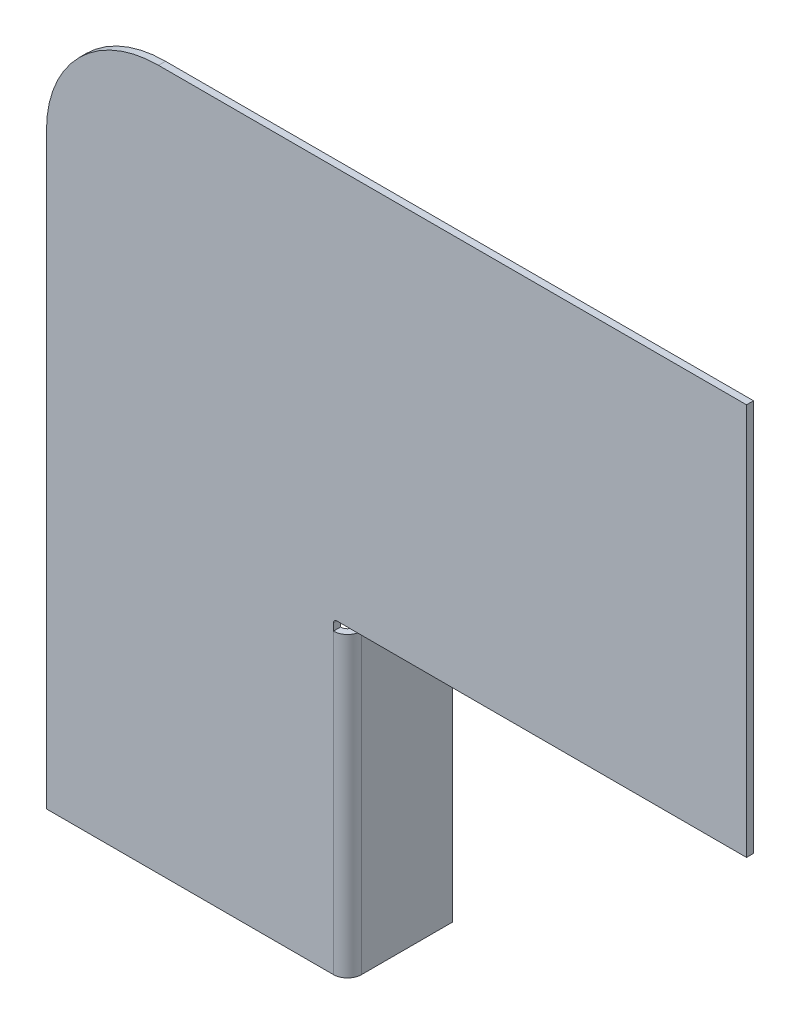
SolidWorks part; units mm, degrees
note: The reader was unsure of these and kept them because the rebuilt part matched: flange length of "Edge-Flange2".
ref_plane "Front Plane" through (0, 0, 0) normal (0, 0, 1) x (1, 0, 0)
ref_plane "Top Plane" through (0, 0, 0) normal (0, 1, 0) x (1, 0, 0)
ref_plane "Right Plane" through (0, 0, 0) normal (1, 0, 0) x (0, 0, -1)
sketch "Sketch1" plane through (0, 0, 0) normal (0, 0, 1) x (1, 0, 0)
  line L0 (-16, 0) -> (-16, -84)
  line L1 (-16, -84) -> (25, -84)
  line L2 (25, -84) -> (25, -40.5)
  line L3 (0, 16) -> (84, 16)
  line L4 (84, 16) -> (84, -40)
  line L5 (84, -40) -> (25.5, -40)
  arc A1 (0, 16) -> (-16, 0) centre (0, 0) ccw
  arc A2 (25.5, -40) -> (25, -40.5) centre (25.5, -40.5) ccw
  point P8 (42, -55)
  point P10 (42, -55)
  dimension "D1" = 56
  dimension "D4" = 1
  dimension "D5" = 41
  dimension "D6" = 16
  dimension "D2" = 84
  dimension "D3" = 84
base flange "Base-Flange1" sketch "Sketch1" thickness 1 reverse thickness direction no parameters "D1"=1
edge flange "Edge-Flange1" [suppressed] sketch "Sketch8" flange profiles "Sketch8", "Sketch10" flange angle 90 flange position material inside bend radius 1 thickness 1
sketch "Sketch8" plane through (0, -4, -1) normal (0, -1, 0) x (-1, 0, 0)
  line L0 (-19, 0) -> (-84, 0) construction
  line L1 (-19, 0) -> (-84, 0)
  line L2 (-84, 0) -> (-84, 19)
  line L3 (-84, 19) -> (-19, 19)
  line L4 (-19, 19) -> (-19, 0)
sketch "Sketch10" plane through (4, 0, -1) normal (1, 0, 0) x (0, -1, 0)
  line L0 (84, 0) -> (19, 0) construction
  line L1 (84, 0) -> (19, 0)
  line L2 (19, 0) -> (19, 19)
  line L3 (19, 19) -> (84, 19)
  line L4 (84, 19) -> (84, 0)
bend "EdgeBend1" bend radius 1 bend angle 90 parameters "D5"=1
bend "EdgeBend2" bend radius 1 bend angle 90 parameters "D5"=3, "D6"=10, "D7"=20
edge flange "Edge-Flange2" sketch "Sketch13" flange angle 90 flange length 15 flange position bend outside bend radius 1 thickness 1 relief rectangular parameters "D6"=10
sketch "Sketch13" plane through (25, 0, -1) normal (1, 0, 0) x (0, -1, 0)
  line L0 (84, 0) -> (40.5, 0) construction
  line L1 (84, 0) -> (41.5, 0)
  line L2 (41.5, 0) -> (41.5, 14)
  line L3 (41.5, 14) -> (84, 14)
  line L4 (84, 14) -> (84, 0)
  line L5 (40.5, 0) -> (40.5, -1) construction
  dimension "D1" = 14
  dimension "D2" = 1
bend "EdgeBend3" bend radius 1 bend angle 90 parameters "D5"=1
sketch "Bend-Lines1" [suppressed] plane through (0, 0, 0) normal (0, 1, 0) x (1, 0, 0)
sketch "Bounding-Box1" [suppressed] plane through (0, 0, 0) normal (0, 1, 0) x (1, 0, 0)
sheet metal parameters "Sheet-Metal1" thickness 1 parameters "D1"=1
flat pattern "Flat-Pattern1" [suppressed]
sketch "Bend-Lines2" plane through (0, 0, 0) normal (0, 1, 0) x (1, 0, 0)
sketch3d "Bounding-Box2" [suppressed]
  line L0 (84, -84, 0) -> (84, 16, 0) construction
  line L1 (-16, -84, 0) -> (-16, 16, 0) construction
  line L2 (84, -84, 0) -> (-16, -84, 0) construction
  line L3 (84, 16, 0) -> (-16, 16, 0) construction
sheet metal parameters "Sheet-Metal2" thickness 1 parameters "D1"=1
flat pattern "Flat-Pattern1"
sketch "Bend-Lines2" plane through (0, 0, 0) normal (0, 0, 1) x (1, 0, 0)
  line L0 (19, -3.1781) -> (84, -3.1781) construction
  line L1 (19, -3.1781) -> (84, -3.1781) construction
  line L2 (3.1781, -84) -> (3.1781, -19) construction
  line L3 (3.1781, -84) -> (3.1781, -19) construction
sketch3d "Bounding-Box2" [suppressed]
  line L0 (84, -84, 0) -> (84, 16, 0) construction
  line L1 (-16, -84, 0) -> (-16, 16, 0) construction
  line L2 (84, -84, 0) -> (-16, -84, 0) construction
  line L3 (84, 16, 0) -> (-16, 16, 0) construction
bend of the flat pattern "Flatten-<EdgeBend1>1"
bend of the flat pattern "Flatten-<EdgeBend2>1"
sheet metal parameters "Sheet-Metal3" thickness 1 parameters "D1"=1
flat pattern "Flat-Pattern1"
sketch "Bend-Lines2" plane through (0, 0, 0) normal (0, 0, 1) x (1, 0, 0)
  line L0 (26.1781, -84) -> (26.1781, -41.5) construction
  line L1 (26.1781, -84) -> (26.1781, -41.5) construction
sketch3d "Bounding-Box2" [suppressed]
  line L0 (84, -84, 0) -> (84, 16, 0) construction
  line L1 (-16, -84, 0) -> (-16, 16, 0) construction
  line L2 (84, -84, 0) -> (-16, -84, 0) construction
  line L3 (84, 16, 0) -> (-16, 16, 0) construction
bend of the flat pattern "Flatten-<EdgeBend3>1"
